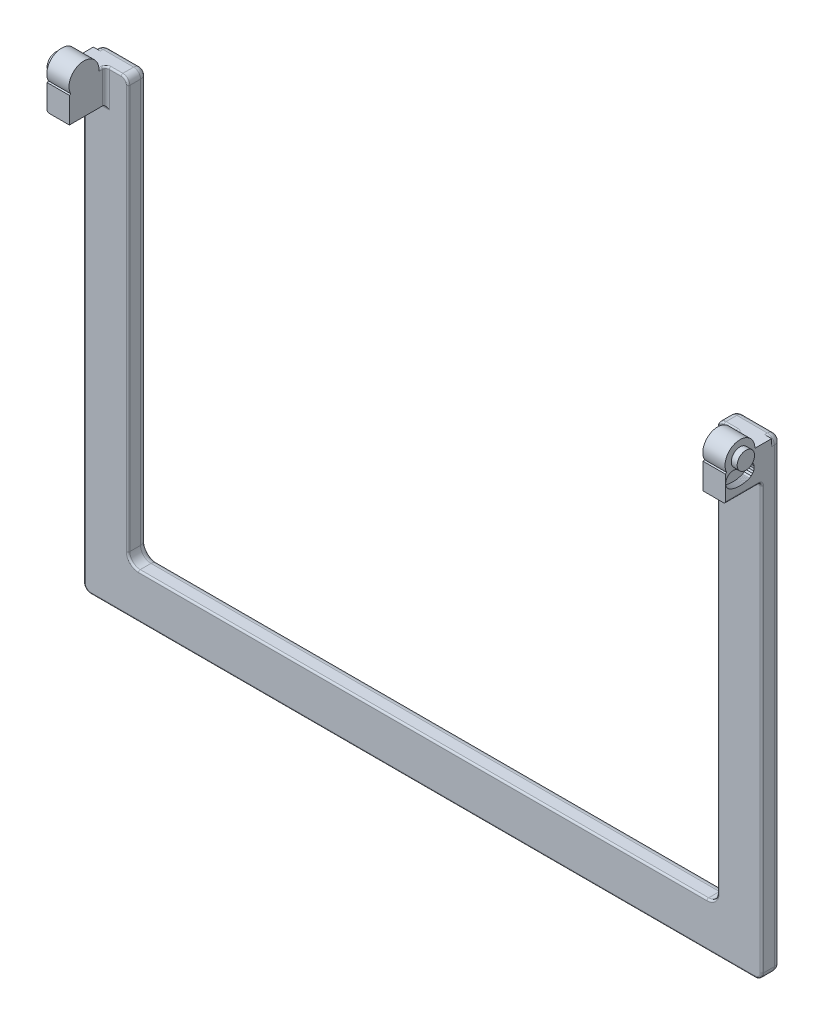
SolidWorks part; units mm, degrees
ref_plane "Спереди" through (0, 0, 0) normal (0, 0, 1) x (1, 0, 0)
ref_plane "Сверху" through (0, 0, 0) normal (0, 1, 0) x (1, 0, 0)
ref_plane "Справа" through (0, 0, 0) normal (1, 0, 0) x (0, 0, -1)
other "Configuration Table"
sketch "Left_leg_profile" plane through (0, 0, 0) normal (0, 0, 1) x (1, 0, 0)
  line L0 (-0.6, -6.6) -> (8.2, -6.6)
  line L1 (10.2, -4.6) -> (10.2, 123)
  line L2 (8.2, 125) -> (-0.6, 125)
  line L3 (-2.6, 123) -> (-2.6, -4.6)
  arc A0 (8.2, -6.6) -> (10.2, -4.6) centre (8.2, -4.6) ccw
  arc A1 (10.2, 123) -> (8.2, 125) centre (8.2, 123) ccw
  arc A2 (-0.6, 125) -> (-2.6, 123) centre (-0.6, 123) ccw
  arc A3 (-2.6, -4.6) -> (-0.6, -6.6) centre (-0.6, -4.6) ccw
extrude "Left_leg" add sketch "Left_leg_profile" along normal blind 5.6 from offset 18.1 offset against normal yes
sketch "Foot_crossbar_profile" plane through (0, 0, 0) normal (0, 0, 1) x (1, 0, 0)
  line L0 (-0.6, -9) -> (190.6, -9)
  line L1 (192.6, -7) -> (192.6, 1.8)
  line L2 (190.6, 3.8) -> (-0.6, 3.8)
  line L3 (-2.6, 1.8) -> (-2.6, -7)
  arc A0 (190.6, -9) -> (192.6, -7) centre (190.6, -7) ccw
  arc A1 (192.6, 1.8) -> (190.6, 3.8) centre (190.6, 1.8) ccw
  arc A2 (-0.6, 3.8) -> (-2.6, 1.8) centre (-0.6, 1.8) ccw
  arc A3 (-2.6, -7) -> (-0.6, -9) centre (-0.6, -7) ccw
extrude "Foot_crossbar" add sketch "Foot_crossbar_profile" along normal blind 5.6 from offset 18.1 offset against normal yes
sketch "Right_leg_profile" plane through (0, 0, 0) normal (0, 0, 1) x (1, 0, 0)
  line L0 (181.8, -6.6) -> (190.6, -6.6)
  line L1 (192.6, -4.6) -> (192.6, 123)
  line L2 (190.6, 125) -> (181.8, 125)
  line L3 (179.8, 123) -> (179.8, -4.6)
  arc A0 (190.6, -6.6) -> (192.6, -4.6) centre (190.6, -4.6) ccw
  arc A1 (192.6, 123) -> (190.6, 125) centre (190.6, 123) ccw
  arc A2 (181.8, 125) -> (179.8, 123) centre (181.8, 123) ccw
  arc A3 (179.8, -4.6) -> (181.8, -6.6) centre (181.8, -4.6) ccw
extrude "Right_leg" add sketch "Right_leg_profile" along normal blind 5.6 from offset 18.1 offset against normal yes
sketch "Pivot_neck_0_profile" plane through (0, 0, 0) normal (1, 0, 0) x (0, 0, -1)
  line L0 (15.3, 115.4) -> (15.3, 125)
  line L1 (15.3, 125) -> (6.2, 125)
  line L2 (6.2, 125) -> (2, 122.8)
  line L3 (2, 122.8) -> (2, 115.4)
  line L4 (2, 115.4) -> (15.3, 115.4)
extrude "Pivot_neck_0" add sketch "Pivot_neck_0_profile" along normal blind 6.4 from offset 2.6 offset against normal yes
sketch "Pivot_lug_0_profile" plane through (0, 0, 0) normal (1, 0, 0) x (0, 0, -1)
  circle A0 centre (6.2, 125) radius 4.3
extrude "Pivot_lug_0" add sketch "Pivot_lug_0_profile" along normal blind 6.4 from offset 2.6 offset against normal yes
sketch "Captive_axle_0_profile" plane through (0, 0, 0) normal (1, 0, 0) x (0, 0, -1)
  circle A0 centre (6.2, 125) radius 2.5
extrude "Captive_axle_0" add sketch "Captive_axle_0_profile" along normal blind 2 from offset 4.3 offset against normal yes
sketch "Blind_rotation_groove_0_profile" plane through (0, 0, 0) normal (1, 0, 0) x (0, 0, -1)
  line L0 (8.9553, 118.3481) -> (8.7362, 118.2615)
  line L1 (8.7362, 118.2615) -> (8.5144, 118.1821)
  line L2 (8.5144, 118.1821) -> (8.29, 118.11)
  line L3 (8.29, 118.11) -> (8.0635, 118.0453)
  line L4 (8.0635, 118.0453) -> (7.8349, 117.9881)
  line L5 (7.8349, 117.9881) -> (7.6047, 117.9383)
  line L6 (7.6047, 117.9383) -> (7.3728, 117.8962)
  line L7 (7.3728, 117.8962) -> (7.1398, 117.8616)
  line L8 (7.1398, 117.8616) -> (6.9057, 117.8347)
  line L9 (6.9057, 117.8347) -> (6.6709, 117.8154)
  line L10 (6.6709, 117.8154) -> (6.4356, 117.8039)
  line L11 (6.4356, 117.8039) -> (6.2, 117.8)
  line L12 (6.2, 117.8) -> (5.9644, 117.8039)
  line L13 (5.9644, 117.8039) -> (5.7291, 117.8154)
  line L14 (5.7291, 117.8154) -> (5.4943, 117.8347)
  line L15 (5.4943, 117.8347) -> (5.2602, 117.8616)
  line L16 (5.2602, 117.8616) -> (5.0272, 117.8962)
  line L17 (5.0272, 117.8962) -> (4.7953, 117.9383)
  line L18 (4.7953, 117.9383) -> (4.5651, 117.9881)
  line L19 (4.5651, 117.9881) -> (4.3365, 118.0453)
  line L20 (4.3365, 118.0453) -> (4.11, 118.11)
  line L21 (4.11, 118.11) -> (3.8856, 118.1821)
  line L22 (3.8856, 118.1821) -> (3.6638, 118.2615)
  line L23 (3.6638, 118.2615) -> (3.4447, 118.3481)
  line L24 (3.4447, 118.3481) -> (2.9473, 118.6352)
  line L25 (2.9473, 118.6352) -> (2.5412, 119.0413)
  line L26 (2.5412, 119.0413) -> (2.254, 119.5387)
  line L27 (2.254, 119.5387) -> (2.1054, 120.0934)
  line L28 (2.1054, 120.0934) -> (2.1054, 120.6678)
  line L29 (2.1054, 120.6678) -> (2.254, 121.2225)
  line L30 (2.254, 121.2225) -> (2.5412, 121.7199)
  line L31 (2.5412, 121.7199) -> (2.9473, 122.126)
  line L32 (2.9473, 122.126) -> (3.4447, 122.4131)
  line L33 (3.4447, 122.4131) -> (3.9994, 122.5618)
  line L34 (3.9994, 122.5618) -> (4.5737, 122.5618)
  line L35 (4.5737, 122.5618) -> (5.1285, 122.4131)
  line L36 (5.1285, 122.4131) -> (5.2137, 122.3795)
  line L37 (5.2137, 122.3795) -> (5.3, 122.3486)
  line L38 (5.3, 122.3486) -> (5.3872, 122.3206)
  line L39 (5.3872, 122.3206) -> (5.4753, 122.2954)
  line L40 (5.4753, 122.2954) -> (5.5642, 122.2731)
  line L41 (5.5642, 122.2731) -> (5.6537, 122.2538)
  line L42 (5.6537, 122.2538) -> (5.7439, 122.2374)
  line L43 (5.7439, 122.2374) -> (5.8345, 122.224)
  line L44 (5.8345, 122.224) -> (5.9256, 122.2135)
  line L45 (5.9256, 122.2135) -> (6.0169, 122.206)
  line L46 (6.0169, 122.206) -> (6.1084, 122.2015)
  line L47 (6.1084, 122.2015) -> (6.2, 122.2)
  line L48 (6.2, 122.2) -> (6.2916, 122.2015)
  line L49 (6.2916, 122.2015) -> (6.3831, 122.206)
  line L50 (6.3831, 122.206) -> (6.4744, 122.2135)
  line L51 (6.4744, 122.2135) -> (6.5655, 122.224)
  line L52 (6.5655, 122.224) -> (6.6561, 122.2374)
  line L53 (6.6561, 122.2374) -> (6.7463, 122.2538)
  line L54 (6.7463, 122.2538) -> (6.8358, 122.2731)
  line L55 (6.8358, 122.2731) -> (6.9247, 122.2954)
  line L56 (6.9247, 122.2954) -> (7.0128, 122.3206)
  line L57 (7.0128, 122.3206) -> (7.1, 122.3486)
  line L58 (7.1, 122.3486) -> (7.1863, 122.3795)
  line L59 (7.1863, 122.3795) -> (7.2715, 122.4131)
  line L60 (7.2715, 122.4131) -> (7.8263, 122.5618)
  line L61 (7.8263, 122.5618) -> (8.4006, 122.5618)
  line L62 (8.4006, 122.5618) -> (8.9553, 122.4131)
  line L63 (8.9553, 122.4131) -> (9.4527, 122.126)
  line L64 (9.4527, 122.126) -> (9.8588, 121.7199)
  line L65 (9.8588, 121.7199) -> (10.146, 121.2225)
  line L66 (10.146, 121.2225) -> (10.2946, 120.6678)
  line L67 (10.2946, 120.6678) -> (10.2946, 120.0934)
  line L68 (10.2946, 120.0934) -> (10.146, 119.5387)
  line L69 (10.146, 119.5387) -> (9.8588, 119.0413)
  line L70 (9.8588, 119.0413) -> (9.4527, 118.6352)
  line L71 (9.4527, 118.6352) -> (8.9553, 118.3481)
extrude "Blind_rotation_groove_0" cut sketch "Blind_rotation_groove_0_profile" along normal blind 2.1 from offset 2.7 offset against normal yes
sketch "Pivot_neck_1_profile" plane through (0, 0, 0) normal (1, 0, 0) x (0, 0, -1)
  line L0 (15.3, 115.4) -> (15.3, 125)
  line L1 (15.3, 125) -> (6.2, 125)
  line L2 (6.2, 125) -> (2, 122.8)
  line L3 (2, 122.8) -> (2, 115.4)
  line L4 (2, 115.4) -> (15.3, 115.4)
extrude "Pivot_neck_1" add sketch "Pivot_neck_1_profile" along normal blind 6.4 from offset 186.2
sketch "Pivot_lug_1_profile" plane through (0, 0, 0) normal (1, 0, 0) x (0, 0, -1)
  circle A0 centre (6.2, 125) radius 4.3
extrude "Pivot_lug_1" add sketch "Pivot_lug_1_profile" along normal blind 6.4 from offset 186.2
sketch "Captive_axle_1_profile" plane through (0, 0, 0) normal (1, 0, 0) x (0, 0, -1)
  circle A0 centre (6.2, 125) radius 2.5
extrude "Captive_axle_1" add sketch "Captive_axle_1_profile" along normal blind 2 from offset 192.3
sketch "Blind_rotation_groove_1_profile" plane through (0, 0, 0) normal (1, 0, 0) x (0, 0, -1)
  line L0 (8.9553, 118.3481) -> (8.7362, 118.2615)
  line L1 (8.7362, 118.2615) -> (8.5144, 118.1821)
  line L2 (8.5144, 118.1821) -> (8.29, 118.11)
  line L3 (8.29, 118.11) -> (8.0635, 118.0453)
  line L4 (8.0635, 118.0453) -> (7.8349, 117.9881)
  line L5 (7.8349, 117.9881) -> (7.6047, 117.9383)
  line L6 (7.6047, 117.9383) -> (7.3728, 117.8962)
  line L7 (7.3728, 117.8962) -> (7.1398, 117.8616)
  line L8 (7.1398, 117.8616) -> (6.9057, 117.8347)
  line L9 (6.9057, 117.8347) -> (6.6709, 117.8154)
  line L10 (6.6709, 117.8154) -> (6.4356, 117.8039)
  line L11 (6.4356, 117.8039) -> (6.2, 117.8)
  line L12 (6.2, 117.8) -> (5.9644, 117.8039)
  line L13 (5.9644, 117.8039) -> (5.7291, 117.8154)
  line L14 (5.7291, 117.8154) -> (5.4943, 117.8347)
  line L15 (5.4943, 117.8347) -> (5.2602, 117.8616)
  line L16 (5.2602, 117.8616) -> (5.0272, 117.8962)
  line L17 (5.0272, 117.8962) -> (4.7953, 117.9383)
  line L18 (4.7953, 117.9383) -> (4.5651, 117.9881)
  line L19 (4.5651, 117.9881) -> (4.3365, 118.0453)
  line L20 (4.3365, 118.0453) -> (4.11, 118.11)
  line L21 (4.11, 118.11) -> (3.8856, 118.1821)
  line L22 (3.8856, 118.1821) -> (3.6638, 118.2615)
  line L23 (3.6638, 118.2615) -> (3.4447, 118.3481)
  line L24 (3.4447, 118.3481) -> (2.9473, 118.6352)
  line L25 (2.9473, 118.6352) -> (2.5412, 119.0413)
  line L26 (2.5412, 119.0413) -> (2.254, 119.5387)
  line L27 (2.254, 119.5387) -> (2.1054, 120.0934)
  line L28 (2.1054, 120.0934) -> (2.1054, 120.6678)
  line L29 (2.1054, 120.6678) -> (2.254, 121.2225)
  line L30 (2.254, 121.2225) -> (2.5412, 121.7199)
  line L31 (2.5412, 121.7199) -> (2.9473, 122.126)
  line L32 (2.9473, 122.126) -> (3.4447, 122.4131)
  line L33 (3.4447, 122.4131) -> (3.9994, 122.5618)
  line L34 (3.9994, 122.5618) -> (4.5737, 122.5618)
  line L35 (4.5737, 122.5618) -> (5.1285, 122.4131)
  line L36 (5.1285, 122.4131) -> (5.2137, 122.3795)
  line L37 (5.2137, 122.3795) -> (5.3, 122.3486)
  line L38 (5.3, 122.3486) -> (5.3872, 122.3206)
  line L39 (5.3872, 122.3206) -> (5.4753, 122.2954)
  line L40 (5.4753, 122.2954) -> (5.5642, 122.2731)
  line L41 (5.5642, 122.2731) -> (5.6537, 122.2538)
  line L42 (5.6537, 122.2538) -> (5.7439, 122.2374)
  line L43 (5.7439, 122.2374) -> (5.8345, 122.224)
  line L44 (5.8345, 122.224) -> (5.9256, 122.2135)
  line L45 (5.9256, 122.2135) -> (6.0169, 122.206)
  line L46 (6.0169, 122.206) -> (6.1084, 122.2015)
  line L47 (6.1084, 122.2015) -> (6.2, 122.2)
  line L48 (6.2, 122.2) -> (6.2916, 122.2015)
  line L49 (6.2916, 122.2015) -> (6.3831, 122.206)
  line L50 (6.3831, 122.206) -> (6.4744, 122.2135)
  line L51 (6.4744, 122.2135) -> (6.5655, 122.224)
  line L52 (6.5655, 122.224) -> (6.6561, 122.2374)
  line L53 (6.6561, 122.2374) -> (6.7463, 122.2538)
  line L54 (6.7463, 122.2538) -> (6.8358, 122.2731)
  line L55 (6.8358, 122.2731) -> (6.9247, 122.2954)
  line L56 (6.9247, 122.2954) -> (7.0128, 122.3206)
  line L57 (7.0128, 122.3206) -> (7.1, 122.3486)
  line L58 (7.1, 122.3486) -> (7.1863, 122.3795)
  line L59 (7.1863, 122.3795) -> (7.2715, 122.4131)
  line L60 (7.2715, 122.4131) -> (7.8263, 122.5618)
  line L61 (7.8263, 122.5618) -> (8.4006, 122.5618)
  line L62 (8.4006, 122.5618) -> (8.9553, 122.4131)
  line L63 (8.9553, 122.4131) -> (9.4527, 122.126)
  line L64 (9.4527, 122.126) -> (9.8588, 121.7199)
  line L65 (9.8588, 121.7199) -> (10.146, 121.2225)
  line L66 (10.146, 121.2225) -> (10.2946, 120.6678)
  line L67 (10.2946, 120.6678) -> (10.2946, 120.0934)
  line L68 (10.2946, 120.0934) -> (10.146, 119.5387)
  line L69 (10.146, 119.5387) -> (9.8588, 119.0413)
  line L70 (9.8588, 119.0413) -> (9.4527, 118.6352)
  line L71 (9.4527, 118.6352) -> (8.9553, 118.3481)
extrude "Blind_rotation_groove_1" cut sketch "Blind_rotation_groove_1_profile" along normal blind 2.1 from offset 190.6
fillet "Stand_leg_root_round" radius 3 2 edges at (10.2, 3.8, -15.3) (179.8, 3.8, -15.3)
fillet "Pivot_neck_root_round" radius 1 4 edges at (0.6, 115.4, -12.5) (3.8, 120.2, -12.5) (189.4, 115.4, -12.5) (186.2, 120.2, -12.5)
fillet "Stand_contact_round" radius 2 16 edges at (-2.0142, 124.4142, -18.1) (192.0142, 124.4142, -18.1) (3.8, 125, -18.1) (9.6142, 124.4142, -18.1) (-2.6, 58, -18.1) (10.2, 64.9, -18.1) (-2.0142, -8.4142, -18.1) (11.0787, 4.6787, -18.1) (95, -9, -18.1) (95, 3.8, -18.1) (192.0142, -8.4142, -18.1) (178.9213, 4.6787, -18.1) (192.6, 58, -18.1) (179.8, 64.9, -18.1) (180.3858, 124.4142, -18.1) (186.2, 125, -18.1)
fillet "Stand_front_edge_round" radius 0.5 22 edges at (-2.6, 115.4, -6.75) (-2.6, 115.1071, -12.2071) (192.6, 115.4, -6.75) (192.6, 115.1071, -12.2071) (186.2, 125, -11) (185.9071, 125, -12.2071) (183.5, 125, -12.5) (180.3858, 124.4142, -12.5) (3.8, 125, -11) (4.0929, 125, -12.2071) (6.5, 125, -12.5) (9.6142, 124.4142, -12.5) (-2.6, 53.7, -12.5) (10.2, 64.9, -12.5) (-2.0142, -8.4142, -12.5) (11.0787, 4.6787, -12.5) (95, -9, -12.5) (95, 3.8, -12.5) (192.0142, -8.4142, -12.5) (178.9213, 4.6787, -12.5) (192.6, 53.7, -12.5) (179.8, 64.9, -12.5)
